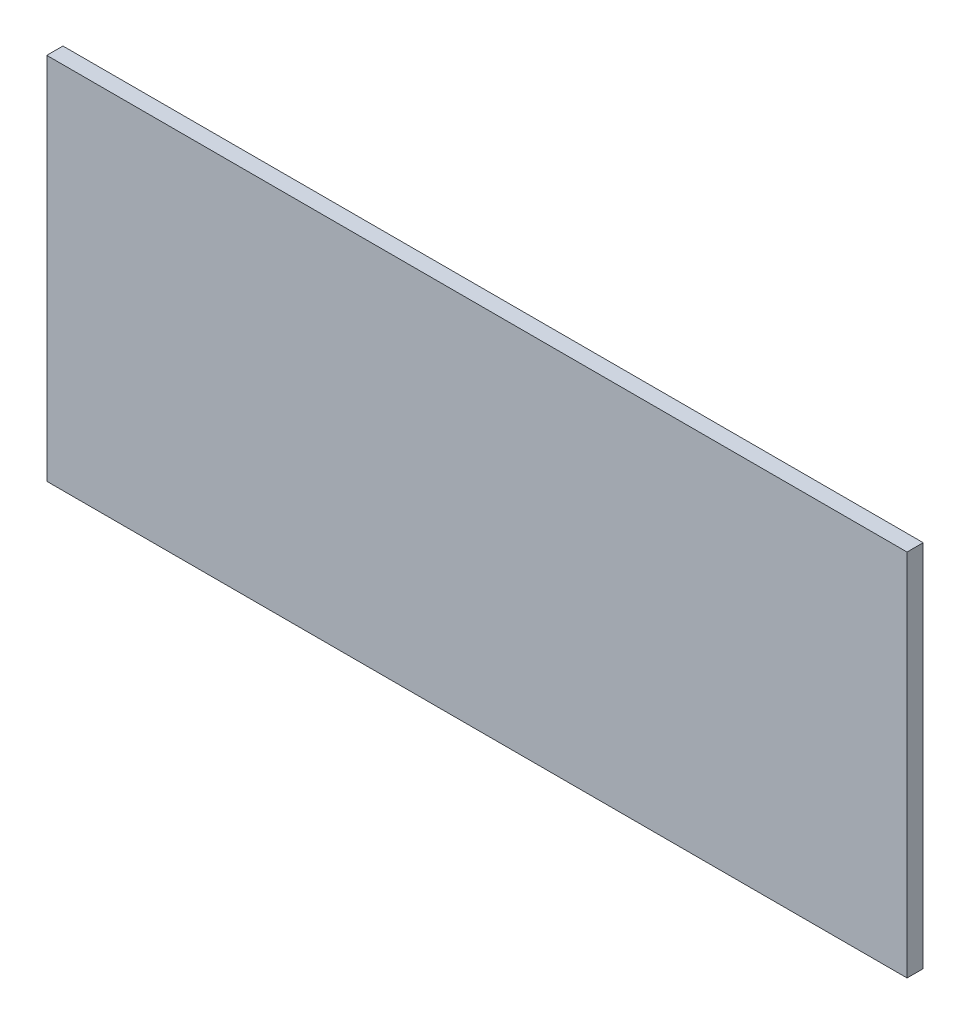
SolidWorks part; units mm, degrees
ref_plane "Front Plane" through (0, 0, 0) normal (0, 0, 1) x (1, 0, 0)
ref_plane "Top Plane" through (0, 0, 0) normal (0, 1, 0) x (1, 0, 0)
ref_plane "Right Plane" through (0, 0, 0) normal (1, 0, 0) x (0, 0, -1)
sketch "Sketch2" plane through (0, 0, 0) normal (0, 0, 1) x (1, 0, 0)
  line L1 (-79.7873, -34.2134) -> (79.7873, -34.2134)
  line L2 (-79.7873, -34.2134) -> (-79.7873, 34.2134)
  line L3 (-79.7873, 34.2134) -> (79.7873, 34.2134)
  line L4 (79.7873, -34.2134) -> (79.7873, 34.2134)
  line L5 (-79.7873, -34.2134) -> (79.7873, 34.2134) construction
  line L6 (-79.7873, 34.2134) -> (79.7873, -34.2134) construction
  point P0 (0, 0)
base flange "Base-Flange1" sketch "Sketch2" thickness 3 reverse thickness direction no parameters "D1"=0.7366
sketch "Bend-Lines1" [suppressed] plane through (0, 0, 0) normal (0, 1, 0) x (1, 0, 0)
sketch "Bounding-Box1" [suppressed] plane through (0, 0, 0) normal (0, 1, 0) x (1, 0, 0)
sheet metal parameters "Sheet-Metal1" thickness 3 parameters "D1"=0.7366
flat pattern "Flat-Pattern1" [suppressed]
sketch "Bend-Lines2" plane through (0, 0, 0) normal (0, 1, 0) x (1, 0, 0)
sketch3d "Bounding-Box2" [suppressed]
  line L0 (79.7873, -34.2134, 0) -> (-79.7873, -34.2134, 0) construction
  line L1 (79.7873, 34.2134, 0) -> (-79.7873, 34.2134, 0) construction
  line L2 (79.7873, -34.2134, 0) -> (79.7873, 34.2134, 0) construction
  line L3 (-79.7873, -34.2134, 0) -> (-79.7873, 34.2134, 0) construction
